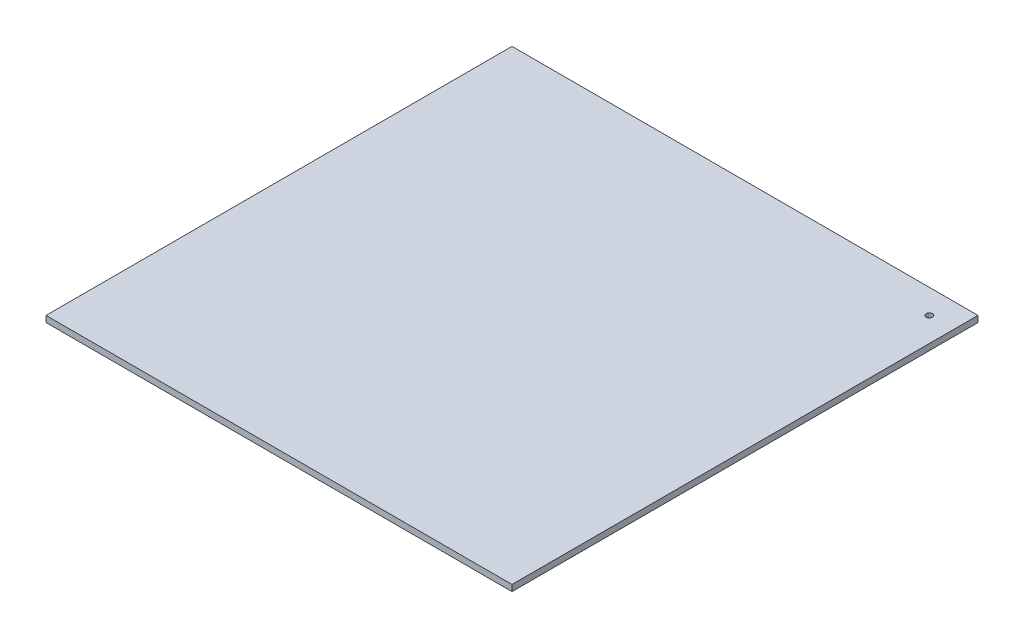
SolidWorks part; units mm, degrees
ref_plane "Front Plane" through (0, 0, 0) normal (0, 0, 1) x (1, 0, 0)
ref_plane "Top Plane" through (0, 0, 0) normal (0, 1, 0) x (1, 0, 0)
ref_plane "Right Plane" through (0, 0, 0) normal (1, 0, 0) x (0, 0, -1)
sketch "Sketch1" plane through (0, 0, 0) normal (0, 1, 0) x (1, 0, 0)
  line L0 (99.3613, 29.3962) -> (99.3613, 329.3962) construction
  line L1 (-50.6387, 329.3962) -> (249.3613, 329.3962)
  line L2 (-50.6387, 329.3962) -> (-50.6387, 29.3962)
  line L3 (-50.6387, 29.3962) -> (249.3613, 29.3962)
  line L4 (249.3613, 329.3962) -> (249.3613, 29.3962)
  line L5 (249.3613, 179.3962) -> (-50.6387, 179.3962) construction
  line L6 (-50.6387, 89.3962) -> (249.3613, 89.3962) construction
  line L7 (53.9399, 329.3962) -> (53.9399, 29.3962) construction
  line L8 (293.9399, 224.8175) -> (-6.0601, 224.8175) construction
  line L9 (189.3613, -15.1825) -> (189.3613, 284.8175) construction
  line L10 (249.3613, 329.3962) -> (-50.6387, 29.3962) construction
  line L11 (-50.6387, 329.3962) -> (249.3613, 29.3962) construction
  line L12 (-23.1637, 272.6462) -> (221.8863, 272.6462) construction
  line L13 (-23.1637, 272.6462) -> (-23.1637, 188.8962) construction
  line L14 (221.8863, 272.6462) -> (221.8863, 86.1462) construction
  line L15 (-23.1637, 86.1462) -> (221.8863, 86.1462) construction
  line L16 (-23.1637, 272.6462) -> (221.8863, 86.1462) construction
  line L17 (221.8863, 272.6462) -> (-23.1637, 86.1462) construction
  line L18 (-33.1637, 185.6462) -> (-33.1637, 188.8962) construction
  line L19 (-23.1637, 169.8962) -> (-33.1637, 169.8962) construction
  line L21 (-23.1637, 188.8962) -> (-33.1637, 188.8962) construction
  line L22 (-33.1637, 169.8962) -> (-33.1637, 173.1462) construction
  line L23 (-33.1637, 185.6462) -> (-50.6387, 185.6462) construction
  line L25 (-33.1637, 173.1462) -> (-50.6387, 173.1462) construction
  line L26 (-50.6387, 185.6462) -> (-50.6387, 173.1462) construction
  line L27 (-33.1637, 185.6462) -> (-50.6387, 173.1462) construction
  line L28 (-33.1637, 173.1462) -> (-50.6387, 185.6462) construction
  line L29 (-23.1637, 169.8962) -> (-23.1637, 86.1462) construction
  circle A0 centre (-16.7587, 179.3962) radius 10.02 construction
  arc A1 (26.1613, 183.0207) -> (26.1613, 175.7716) centre (16.8413, 179.3962) ccw construction
  circle A2 centre (99.3613, 179.3962) radius 10 construction
  circle A3 centre (-34.989, 313.7464) radius 2 construction
  circle A4 centre (233.7116, 313.7464) radius 2
  circle A5 centre (233.7116, 45.0459) radius 2 construction
  circle A6 centre (-34.989, 45.0459) radius 2 construction
  arc A7 (26.1613, 175.7716) -> (26.1613, 183.0207) centre (35.4813, 179.3962) ccw construction
  circle A8 centre (99.3613, 295.5162) radius 10.02 construction
  arc A9 (102.9859, 252.5962) -> (95.7367, 252.5962) centre (99.3613, 261.9162) ccw construction
  arc A10 (95.7367, 252.5962) -> (102.9859, 252.5962) centre (99.3613, 243.2762) ccw construction
  circle A11 centre (215.4813, 179.3962) radius 10.02 construction
  arc A12 (172.5613, 175.7716) -> (172.5613, 183.0207) centre (181.8813, 179.3962) ccw construction
  arc A13 (172.5613, 183.0207) -> (172.5613, 175.7716) centre (163.2413, 179.3962) ccw construction
  circle A14 centre (99.3613, 63.2762) radius 10.02 construction
  arc A15 (95.7367, 106.1962) -> (102.9859, 106.1962) centre (99.3613, 96.8762) ccw construction
  arc A16 (102.9859, 106.1962) -> (95.7367, 106.1962) centre (99.3613, 115.5162) ccw construction
  point P10 (99.3613, 89.3962)
  point P11 (189.3613, 134.8175)
  point P12 (53.9399, 179.3962)
  point P19 (121.6506, 157.1068)
  point P23 (99.3613, 179.3962)
  point P28 (99.3613, 179.3962)
  point P31 (-23.1637, 179.3962)
  point P39 (99.3613, 179.3962)
  point P60 (99.3613, 179.3962)
  point P72 (-41.9012, 179.3962)
  dimension "D5" = 116.12
  dimension "D6" = 82.52
  dimension "D7" = 190
  dimension "D9" = 63.88
  dimension "D1" = 90
  dimension "D3" = 300
  dimension "D4" = 300
  dimension "D11" = 186.5
  dimension "D12" = 245.05
  dimension "D2" = 4
  dimension "D8" = 4
  dimension "D10" = 4
extrude "Boss-Extrude1" add sketch "Sketch1" along normal blind 4
